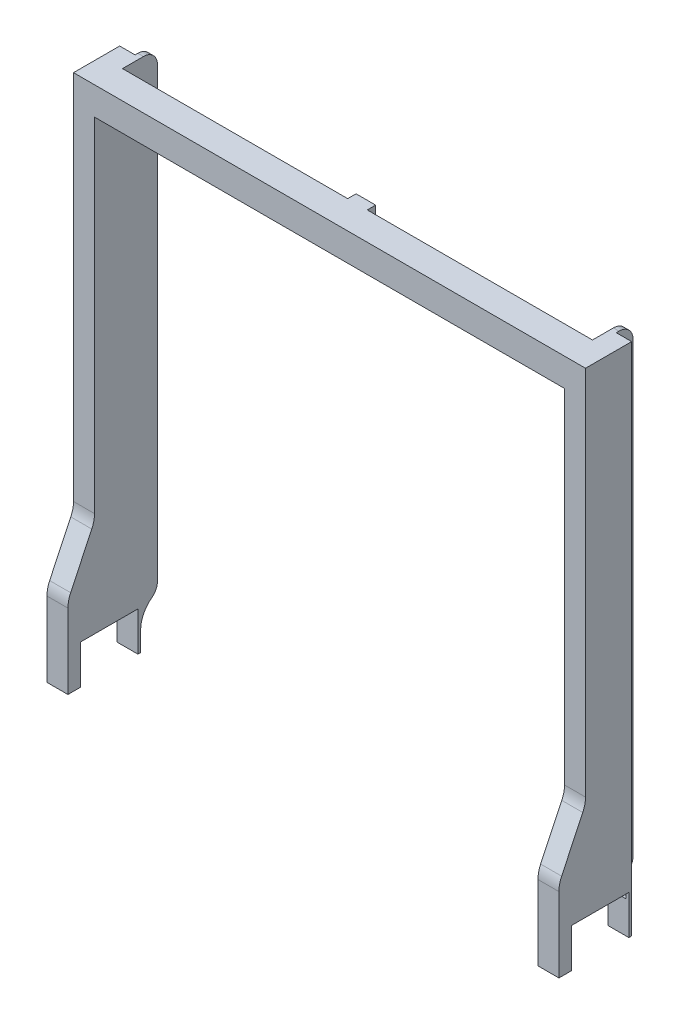
SolidWorks part; units mm, degrees
ref_plane "정면" through (0, 0, 0) normal (0, 0, 1) x (1, 0, 0)
ref_plane "윗면" through (0, 0, 0) normal (0, 1, 0) x (1, 0, 0)
ref_plane "우측면" through (0, 0, 0) normal (1, 0, 0) x (0, 0, -1)
sketch "스케치1" plane through (0, 0, 0) normal (0, 0, 1) x (1, 0, 0)
  line L0 (-318.5049, 0) -> (318.5049, 0) construction
  line L1 (0, 0) -> (0, -258.8265) construction
  line L2 (-168, 0) -> (168, 0)
  line L3 (-168, -20) -> (168, -20)
  line L4 (168, -20) -> (168, 0) construction
  line L5 (168, -20) -> (168, -340)
  line L6 (172, -340) -> (172, 0)
  line L7 (168, 0) -> (183, 0)
  line L8 (183, 0) -> (183, -340)
  line L9 (183, -340) -> (168, -340)
  line L10 (-168, -20) -> (-168, 0) construction
  line L11 (-183, -340) -> (-168, -340)
  line L12 (-183, 0) -> (-183, -340)
  line L13 (-168, 0) -> (-183, 0)
  line L14 (-172, -340) -> (-172, 0)
  line L15 (-168, -20) -> (-168, -340)
  line L16 (168, -20) -> (168, 0)
  line L17 (-168, -20) -> (-168, 0)
  point P14 (0, -20)
  dimension "D1" = 168
  dimension "D2" = 20
  dimension "D3" = 4
  dimension "D4" = 340
  dimension "D5" = 15
extrude "보스-돌출1" add sketch "스케치1" along normal blind 26 contours L3 L5 L9 L8 L7 L2 L13 L12 L11 L15
extrude "보스-돌출2" add sketch "스케치1<4>" against normal blind 19 contours L16 L5 L9 L6 L7 | L15 L17 L13 L14 L11 region at (-170, -170, 0) region at (170, -170, 0)
sketch "스케치1<4>" plane through (0, 0, 0) normal (0, 0, 1) x (1, 0, 0) same geometry as "스케치1"
fillet "필렛1" radius 10 4 edges at (-170, 0, -19) (170, 0, -19) (170, -340, -19) (-170, -340, -19)
sketch "스케치2" plane through (172, 0, 0) normal (1, 0, 0) x (0, 0, -1)
  line L0 (14, -340) -> (14, 0)
  line L1 (12, 0) -> (12, -340)
  line L4 (19, -330) -> (19, -10)
  line L5 (9, 0) -> (0, 0)
  line L6 (0, 0) -> (0, -340)
  line L7 (0, -340) -> (9, -340)
  line L8 (19, -330) -> (19, -10)
  line L9 (9, 0) -> (0, 0)
  line L10 (0, 0) -> (0, -340)
  line L11 (0, -340) -> (9, -340)
  arc A2 (19, -10) -> (9, 0) centre (9, -10) ccw
  arc A3 (9, -340) -> (19, -330) centre (9, -330) ccw
  arc A4 (19, -10) -> (9, 0) centre (9, -10) ccw
  arc A5 (9, -340) -> (19, -330) centre (9, -330) ccw
  dimension "D2" = 5
  dimension "D3" = 2
  dimension "D1" = 0
sketch "스케치3" plane through (168, 0, 0) normal (-1, 0, 0) x (0, 0, 1)
  line L0 (-12, 0) -> (-12, -340) construction
  line L1 (-14, -340) -> (-14, 0) construction
  line L2 (-12, 0) -> (-12, -340)
  line L3 (-14, -340) -> (-14, 0)
  line L4 (-19, -10) -> (-19, -330)
  line L5 (0, 0) -> (-9, 0)
  line L6 (0, -340) -> (0, 0)
  line L7 (-9, -340) -> (0, -340)
  line L8 (-19, -10) -> (-19, -330)
  line L9 (0, 0) -> (-9, 0)
  line L10 (0, -340) -> (0, 0)
  line L11 (-9, -340) -> (0, -340)
  arc A2 (-9, 0) -> (-19, -10) centre (-9, -10) ccw
  arc A3 (-19, -330) -> (-9, -340) centre (-9, -330) ccw
  arc A4 (-9, 0) -> (-19, -10) centre (-9, -10) ccw
  arc A5 (-19, -330) -> (-9, -340) centre (-9, -330) ccw
  dimension "D1" = 0
sketch "스케치5" plane through (0, 0, 0) normal (0, 1, 0) x (1, 0, 0)
  line L0 (-7, 0) -> (-7, -26)
  line L1 (7, 0) -> (7, -26)
  line L2 (-168, 0) -> (-168, -6)
  line L3 (-168, -6) -> (-7, -6)
  line L4 (7, -6) -> (168, -6)
  line L5 (168, -6) -> (168, 0)
  line L12 (-168, 0) -> (-168, 9)
  line L13 (-168, 9) -> (-172, 9)
  line L14 (-172, 9) -> (-172, 0)
  line L15 (-172, 0) -> (-183, 0)
  line L16 (-183, 0) -> (-183, -26)
  line L17 (-183, -26) -> (183, -26)
  line L18 (183, -26) -> (183, 0)
  line L19 (183, 0) -> (172, 0)
  line L20 (172, 0) -> (172, 9)
  line L21 (172, 9) -> (168, 9)
  line L22 (168, 9) -> (168, 0)
  line L23 (168, 0) -> (-168, 0)
  line L24 (-168, 0) -> (-168, 9)
  line L25 (-168, 9) -> (-172, 9)
  line L26 (-172, 9) -> (-172, 0)
  line L27 (-172, 0) -> (-183, 0)
  line L28 (-183, 0) -> (-183, -26)
  line L29 (-183, -26) -> (183, -26)
  line L30 (183, -26) -> (183, 0)
  line L31 (183, 0) -> (172, 0)
  line L32 (172, 0) -> (172, 9)
  line L33 (172, 9) -> (168, 9)
  line L34 (168, 9) -> (168, 0)
  line L35 (168, 0) -> (-168, 0)
  line M27 (168, 0) -> (-168, 0)
  dimension "D2" = 7
  dimension "D3" = 7
  dimension "D4" = 6
  dimension "D1" = 0
extrude "컷-돌출1" cut sketch "스케치5" against normal blind 52 contours L2 L3 L0 M27 | L4 L5 L1 M27 region at (-87.5, 0, 3) region at (87.5, 0, 3)
extrude "보스-돌출4" add sketch "스케치1<5>" against normal blind 7 contours L9 L8 L7 L6 | L11 L14 L13 L12 region at (-177.5, -170, 0) region at (177.5, -170, 0)
sketch "스케치1<5>" plane through (0, 0, 0) normal (0, 0, 1) x (1, 0, 0) same geometry as "스케치1"
sketch "스케치6" plane through (0, -340, 0) normal (0, -1, 0) x (1, 0, 0)
  line L0 (-172, -7) -> (-126.7636, -7) construction
  line L1 (-172, -7) -> (-168, -7)
  line L2 (-168, -7) -> (-168, -5)
  line L3 (-168, -5) -> (-174.5, -5)
  line L4 (-174.5, -5) -> (-174.5, -7)
  line L5 (-181.1, -7) -> (-181.1, -5)
  line L6 (-172, -7) -> (-172, -9)
  line L7 (-172, -9) -> (-168, -9)
  line L8 (-168, -9) -> (-168, 26)
  line L9 (-168, 26) -> (-183, 26)
  line L10 (-183, 26) -> (-183, -7)
  line L11 (-183, -7) -> (-172, -7)
  line L12 (-172, -7) -> (-172, -9)
  line L13 (-172, -9) -> (-168, -9)
  line L14 (-168, -9) -> (-168, 26)
  line L15 (-168, 26) -> (-183, 26)
  line L16 (-183, 26) -> (-183, -7)
  line L17 (-183, -7) -> (-172, -7)
  line L18 (-181.1, -5) -> (-183, -5)
  line L19 (-181.1, -5) -> (-174.5, -5)
  line L20 (-168, 26) -> (-168, 36)
  line L21 (-168, 36) -> (-183, 36)
  line L22 (-183, 36) -> (-183, 26)
  line L23 (-168, 36) -> (-168, 45)
  line L24 (-168, 45) -> (-183, 45)
  line L25 (-183, 45) -> (-183, 36)
  line M14 (-168, -9) -> (-168, 26)
  line M15 (-168, 26) -> (-183, 26)
  line M17 (-183, -7) -> (-172, -7)
  dimension "D2" = 6.5
  dimension "D3" = 2
  dimension "D4" = 6.6
  dimension "D5" = 41
  dimension "D6" = 9
  dimension "D1" = 0
extrude "보스-돌출5" add sketch "스케치6" along normal blind 28 contours L5 L18 L16 M17 | L19 L5 L4 M17 | L3 L4 L1 M17 M14 region at (-171.25, -340, -6) region at (-177.8, -340, -6) region at (-182.05, -340, -6)
extrude "컷-돌출2" cut sketch "스케치6<3>" along normal blind 5 contours L19 L5 L4 M17 region at (-177.8, -340, -6)
sketch "스케치6<3>" plane through (0, -340, 0) normal (0, -1, 0) x (1, 0, 0) same geometry as "스케치6"
fillet "필렛2" radius 20 1 edges at (-170, -340, -7)
extrude "보스-돌출6" add sketch "스케치6<4>" against normal blind 30 contours L21 L22 L20 M15 | L24 L25 L21 L23 region at (-175.5, -340, 31) region at (-175.5, -340, 40.5)
sketch "스케치6<4>" plane through (0, -340, 0) normal (0, -1, 0) x (1, 0, 0) same geometry as "스케치6"
extrude "보스-돌출7" add sketch "스케치6<5>" along normal blind 28 contours L24 L25 L21 L23 region at (-175.5, -340, 40.5)
sketch "스케치6<5>" plane through (0, -340, 0) normal (0, -1, 0) x (1, 0, 0) same geometry as "스케치6"
sketch "스케치9" plane through (-183, 0, 0) normal (-1, 0, 0) x (0, 0, 1)
  line L0 (45, -310) -> (26, -270)
  line L1 (26, 0) -> (26, -310) construction
  line L12 (26, 0) -> (-7, 0)
  line L13 (-7, 0) -> (-7, -368)
  line L14 (-7, -368) -> (-5, -368)
  line L15 (-5, -368) -> (-5, -340)
  line L16 (-5, -340) -> (36, -340)
  line L17 (36, -340) -> (36, -368)
  line L18 (36, -368) -> (45, -368)
  line L19 (45, -368) -> (45, -310)
  line L20 (45, -310) -> (26, -310)
  line L21 (26, -310) -> (26, 0)
  line L22 (26, 0) -> (-7, 0)
  line L23 (-7, 0) -> (-7, -368)
  line L24 (-7, -368) -> (-5, -368)
  line L25 (-5, -368) -> (-5, -340)
  line L26 (-5, -340) -> (36, -340)
  line L27 (36, -340) -> (36, -368)
  line L28 (36, -368) -> (45, -368)
  line L29 (45, -368) -> (45, -310)
  line L30 (45, -310) -> (26, -310)
  line L31 (26, -310) -> (26, 0)
  line M19 (45, -310) -> (26, -310)
  line M20 (26, -310) -> (26, 0)
  dimension "D2" = 40
  dimension "D1" = 0
extrude "보스-돌출8" add sketch "스케치9" against normal blind 15 contours L0 M19 M20 region at (-183, -296.6667, 32.3333)
fillet "필렛3" radius 20 2 edges at (-175.5, -270, 26) (-175.5, -310, 45)
mirror "대칭 복사2" about plane through (0, 0, 0) normal (1, 0, 0) of "보스-돌출5", "컷-돌출2", "필렛3", "보스-돌출6", "보스-돌출7", "보스-돌출8"
fillet "필렛4" radius 20 1 edges at (170, -340, -7)
